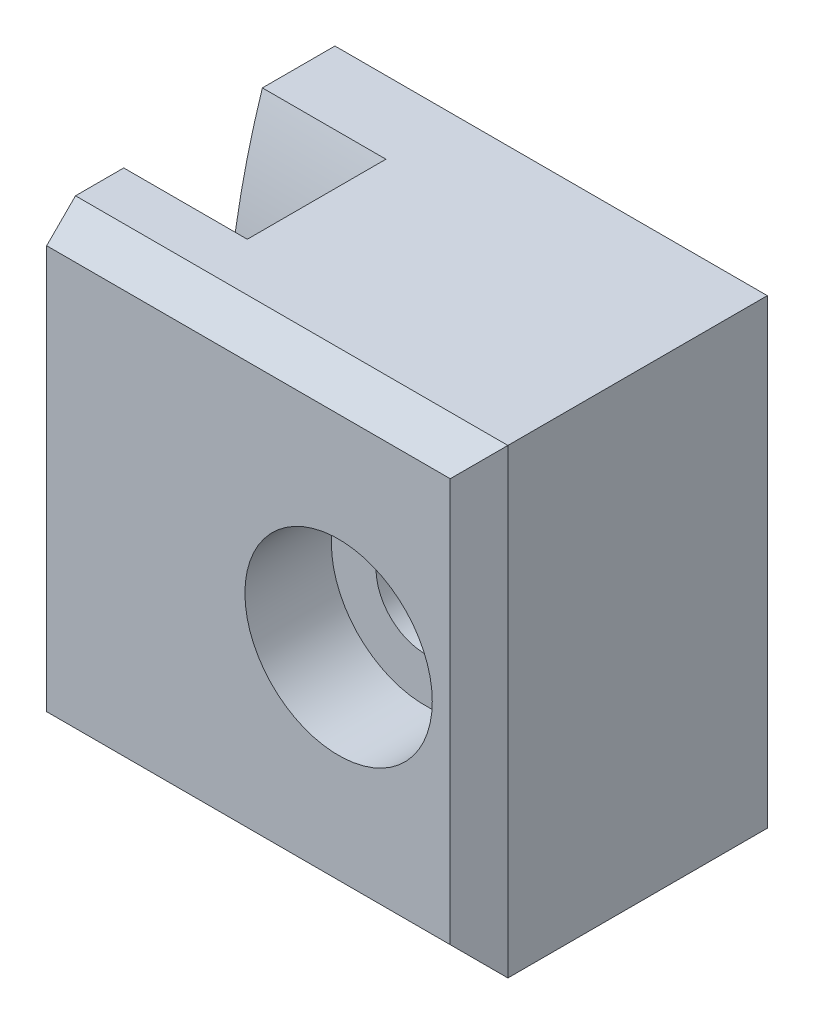
SolidWorks part; units mm, degrees
ref_plane "Plan de face" through (0, 0, 0) normal (0, 0, 1) x (1, 0, 0)
ref_plane "Plan de dessus" through (0, 0, 0) normal (0, 1, 0) x (1, 0, 0)
ref_plane "Plan de droite" through (0, 0, 0) normal (1, 0, 0) x (0, 0, -1)
sketch "Esquisse1" plane through (0, 0, 0) normal (0, 0, 1) x (1, 0, 0)
  line L0 (0, 0) -> (15, 0) construction
  line L1 (0, 8) -> (15, 8)
  line L2 (0, 8) -> (0, -8)
  line L3 (0, -8) -> (15, -8)
  line L4 (15, 8) -> (15, -8)
  dimension "D1" = 16
  dimension "D2" = 15
extrude "Extrusion1" add sketch "Esquisse1" along normal blind 10
sketch "Esquisse2" plane through (0, 0, 0) normal (0, 1, 0) x (1, 0, 0)
  line L0 (27.4388, 27.5) -> (6.4388, 27.5) construction
  line L1 (-1.2431, -8.3975) -> (4.2857, -8.3975)
  line L2 (-1.2431, -8.3975) -> (-1.2431, -3.789)
  line L3 (-1.2431, -3.789) -> (4.2857, -3.789)
  line L4 (4.2857, -8.3975) -> (4.2857, -3.789)
  line L5 (27.4388, 27.5) -> (6.4388, 27.5) construction
  line L6 (6.4388, 16.5) -> (27.4388, 16.5) construction
  line L7 (6.4388, 16.5) -> (27.4388, 16.5) construction
  line L8 (6.5803, 22) -> (25.1183, 22) construction
chamfer "Chanfrein1" distance 1 angle 45 2 edges at (7.5, -8, 10) (7.5, 8, 10)
hole_wizard "Chambrage pour vis à tête hexagonale M31" positions "Esquisse3D1" profile "Esquisse4" counterbore size "M3" standard "ISO" end condition through all
sketch3d "Esquisse3D1"
  line L0 (15, 7, 10) -> (0, 7, 10) construction
  line L1 (15, 7, 10) -> (0, 7, 10)
  line L2 (0, -7, 10) -> (15, -7, 10) construction
  line L3 (0, -7, 10) -> (15, -7, 10)
  line L4 (10.1269, 7, 10) -> (10.1269, -7, 10) construction
  point P0 (10.1269, 0, 10)
sketch "Esquisse4" plane through (10.1269, 0, 10) normal (1, 0, 0) x (0, -1, 0)
  line L0 (0, 0) -> (0, 10)
  line L1 (0, 10) -> (1.7, 10)
  line L3 (1.7, 10) -> (1.7, 3)
  line L4 (1.7, 3) -> (3.25, 3)
  line L5 (3.25, 3) -> (3.25, 0)
  line L7 (3.25, 0) -> (0, 0)
  line L11 (0, -6.35) -> (0, 107.95) construction
  dimension "Diamètre du perçage jusqu'au prochain" = 3.4
  dimension "Profondeur du perçage jusqu'au prochain" = 10
  dimension "Diamètre du chambrage" = 6.5
  dimension "Profondeur du chambrage" = 3
ref_axis "Axe1" through (100.0113, -0.6122, -22) along (-1, 0, 0)
revolve "Enlèvement de matière-Révolution1" cut sketch "Esquisse2" angle 39 mid plane about L8
chamfer "Chanfrein2" distance 1 angle 45 1 edges at (15, 0, 10)
